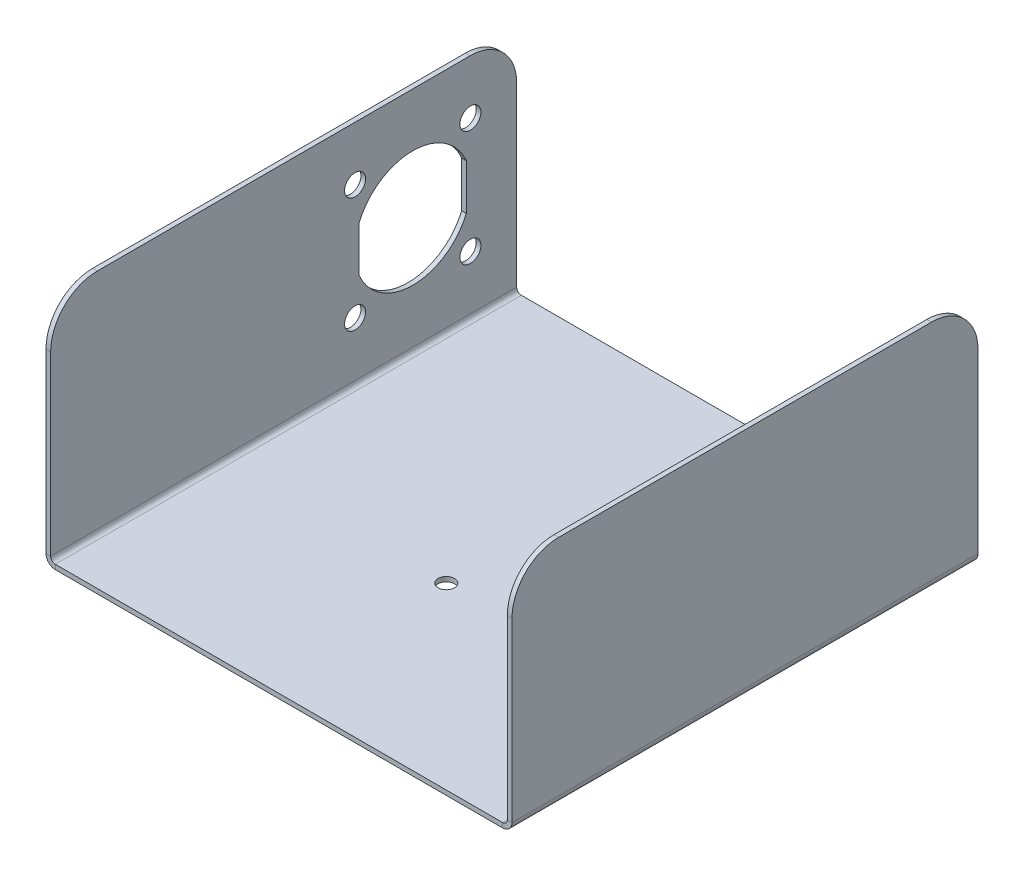
SolidWorks part; units mm, degrees
note: The reader was unsure of these and kept them because the rebuilt part matched: flange length of "Edge-Flange1", "Edge-Flange2".
material "AISI 1020"
ref_plane "Front Plane" through (0, 0, 0) normal (0, 0, 1) x (1, 0, 0)
ref_plane "Top Plane" through (0, 0, 0) normal (0, 1, 0) x (1, 0, 0)
ref_plane "Right Plane" through (0, 0, 0) normal (1, 0, 0) x (0, 0, -1)
sketch "Sketch1" plane through (0, 0, 0) normal (0, 1, 0) x (1, 0, 0)
  line L1 (0, 0) -> (100, 0)
  line L2 (0, 0) -> (0, 100)
  line L3 (0, 100) -> (100, 100)
  line L4 (100, 0) -> (100, 100)
  dimension "D1" = 100
  dimension "D2" = 100
base flange "Base-Flange1" sketch "Sketch1" thickness 1 reverse thickness direction no parameters "D1"=1
edge flange "Edge-Flange1" sketch "Sketch8" flange angle 90 flange length 50 flange position material inside bend radius 1 thickness 1 parameters "D6"=10
sketch "Sketch8" plane through (100, 0, 0) normal (1, 0, 0) x (0, 0, -1)
  line L2 (0, 0) -> (0, 49)
  line L3 (0, 49) -> (100, 49)
  line L4 (100, 49) -> (100, 0)
  line L7 (0, 0) -> (100, 0) construction
  line L8 (0, 0) -> (100, 0)
bend "EdgeBend1" bend radius 1 bend angle 90 parameters "D5"=1
edge flange "Edge-Flange2" sketch "Sketch11" flange angle 90 flange length 50 flange position material inside bend radius 1 thickness 1 parameters "D6"=10
sketch "Sketch11" plane through (0, 0, 0) normal (-1, 0, 0) x (0, 0, 1)
  line L0 (-100, 0) -> (0, 0) construction
  line L1 (-100, 0) -> (0, 0)
  line L2 (-100, 0) -> (-100, 49)
  line L3 (-100, 49) -> (0, 49)
  line L4 (0, 49) -> (0, 0)
bend "EdgeBend2" bend radius 1 bend angle 90 parameters "D5"=2
fillet "Fillet1" radius 10 4 edges at (99.5, 49, -100) (0.5, 49, -100) (99.5, 49, 0) (0.5, 49, 0)
extrude "Cut-Extrude1" cut sketch "Sketch12" against normal blind 10
sketch "Sketch12" plane through (-1, -31.3735, -102.5325) normal (-1, 0, 0) x (0, 0, 1)
  line L0 (2.5325, 32.3735) -> (36.3325, 48.5975) construction
  line L1 (102.5325, 80.3735) -> (2.5325, 80.3735) construction
  line L2 (2.5325, 80.3735) -> (102.5325, 32.3735) construction
  line L3 (102.5325, 56.3735) -> (52.5325, 56.3735) construction
  line L6 (24.8325, 56.3735) -> (18.0954, 63.1106) construction
  line L7 (13.3325, 61.2725) -> (13.3325, 51.4745)
  line L8 (36.3325, 61.2725) -> (36.3325, 51.4745)
  line L9 (52.5325, 56.3735) -> (102.5325, 80.3735) construction
  line L10 (36.3325, 56.3735) -> (2.5325, 56.3735) construction
  arc A0 (13.3325, 51.4745) -> (36.3325, 51.4745) centre (24.8325, 56.3735) ccw
  arc A1 (36.3325, 61.2725) -> (13.3325, 61.2725) centre (24.8325, 56.3735) ccw
  circle A2 centre (12.4581, 68.7479) radius 2.25
  circle A3 centre (37.2068, 68.7479) radius 2.25
  circle A4 centre (37.2068, 43.9992) radius 2.25
  circle A5 centre (12.4581, 43.9992) radius 2.25
  point P34 (24.8325, 56.3735)
extrude "Cut-Extrude2" cut sketch "Sketch13" against normal blind 8
sketch "Sketch13" plane through (17.3133, -1, -102.5325) normal (0, -1, 0) x (1, 0, 0)
  line L0 (42.6867, 102.5243) -> (42.6867, 2.5406) construction
  line L3 (30.1293, 64.0825) -> (42.6867, 56.8325) construction
  line L6 (80.6867, 2.5325) -> (-15.3133, 2.5325) construction
  circle A0 centre (42.6867, 56.8325) radius 3.25
  circle A1 centre (30.1293, 64.0825) radius 1.75
  circle A4 centre (55.244, 64.0825) radius 1.75
  circle A5 centre (42.6867, 42.3325) radius 1.75
  point P16 (42.6867, 56.8325)
sketch "Bend-Lines1" [suppressed] plane through (0, 0, 0) normal (0, 1, 0) x (1, 0, 0)
sketch "Bounding-Box1" [suppressed] plane through (0, 0, 0) normal (0, 1, 0) x (1, 0, 0)
sheet metal parameters "Sheet-Metal1" thickness 1 parameters "D1"=1
flat pattern "Flat-Pattern1" [suppressed]
sketch "Bend-Lines2" plane through (0, 0, 0) normal (0, 1, 0) x (1, 0, 0)
sketch3d "Bounding-Box2" [suppressed]
  line L0 (0, 0, 0) -> (0, 80, 0) construction
  line L1 (-55, 0, 0) -> (-55, 80, 0) construction
  line L2 (0, 0, 0) -> (-55, 0, 0) construction
  line L3 (0, 80, 0) -> (-55, 80, 0) construction
sheet metal parameters "Sheet-Metal2" thickness 1 parameters "D1"=1
flat pattern "Flat-Pattern1"
sketch "Bend-Lines2" plane through (0, 0, 0) normal (0, 1, 0) x (1, 0, 0)
  line L0 (54.1781, 0) -> (54.1781, 80) construction
  line L1 (54.1781, 0) -> (54.1781, 80) construction
sketch3d "Bounding-Box2" [suppressed]
  line L0 (103.3562, 80, 0) -> (0, 80, 0) construction
  line L1 (103.3562, 0, 0) -> (0, 0, 0) construction
  line L2 (103.3562, 80, 0) -> (103.3562, 0, 0) construction
  line L3 (0, 80, 0) -> (0, 0, 0) construction
bend of the flat pattern "Flatten-<EdgeBend1>1"
sheet metal parameters "Sheet-Metal3" thickness 1 parameters "D1"=1
flat pattern "Flat-Pattern1"
sketch "Bend-Lines2" plane through (0, 0, 0) normal (0, 1, 0) x (1, 0, 0)
  line L0 (99.1781, 0) -> (99.1781, 100) construction
  line L1 (99.1781, 0) -> (99.1781, 100) construction
  line L2 (0.8219, 100) -> (0.8219, 0) construction
  line L3 (0.8219, 100) -> (0.8219, 0) construction
sketch3d "Bounding-Box2" [suppressed]
  line L0 (-48.3562, 100, 0) -> (148.3562, 100, 0) construction
  line L1 (-48.3562, 0, 0) -> (148.3562, 0, 0) construction
  line L2 (-48.3562, 100, 0) -> (-48.3562, 0, 0) construction
  line L3 (148.3562, 100, 0) -> (148.3562, 0, 0) construction
bend of the flat pattern "Flatten-<EdgeBend1>1"
bend of the flat pattern "Flatten-<EdgeBend2>1"
sheet metal parameters "Sheet-Metal4" thickness 1 parameters "D1"=1
flat pattern "Flat-Pattern1"
sketch "Bend-Lines2" plane through (0, 0, 0) normal (0, 1, 0) x (1, 0, 0)
  line L0 (99.1781, 0) -> (99.1781, 100) construction
  line L1 (99.1781, 0) -> (99.1781, 100) construction
  line L2 (0.8219, 100) -> (0.8219, 0) construction
  line L3 (0.8219, 100) -> (0.8219, 0) construction
sketch3d "Bounding-Box2" [suppressed]
  line L0 (-48.3562, 100, 0) -> (148.3562, 100, 0) construction
  line L1 (-48.3562, 0, 0) -> (148.3562, 0, 0) construction
  line L2 (-48.3562, 100, 0) -> (-48.3562, 0, 0) construction
  line L3 (148.3562, 100, 0) -> (148.3562, 0, 0) construction
bend of the flat pattern "Flatten-<EdgeBend1>1"
bend of the flat pattern "Flatten-<EdgeBend2>1"
sheet metal parameters "Sheet-Metal5" thickness 1 parameters "D1"=1
flat pattern "Flat-Pattern1"
sketch "Bend-Lines2" plane through (0, 0, 0) normal (0, 1, 0) x (1, 0, 0)
  line L0 (99.1781, 0) -> (99.1781, 100) construction
  line L1 (99.1781, 0) -> (99.1781, 100) construction
  line L2 (0.8219, 100) -> (0.8219, 0) construction
  line L3 (0.8219, 100) -> (0.8219, 0) construction
sketch3d "Bounding-Box2" [suppressed]
  line L0 (-48.3562, 100, 0) -> (148.3562, 100, 0) construction
  line L1 (-48.3562, 0, 0) -> (148.3562, 0, 0) construction
  line L2 (-48.3562, 100, 0) -> (-48.3562, 0, 0) construction
  line L3 (148.3562, 100, 0) -> (148.3562, 0, 0) construction
bend of the flat pattern "Flatten-<EdgeBend1>1"
bend of the flat pattern "Flatten-<EdgeBend2>1"
